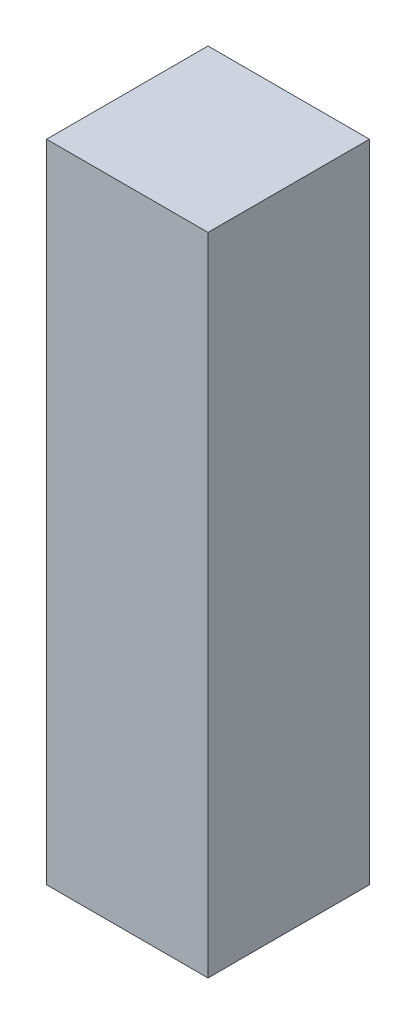
SolidWorks part; units mm, degrees
ref_plane "Front Plane" through (0, 0, 0) normal (0, 0, 1) x (1, 0, 0)
ref_plane "Top Plane" through (0, 0, 0) normal (0, 1, 0) x (1, 0, 0)
ref_plane "Right Plane" through (0, 0, 0) normal (1, 0, 0) x (0, 0, -1)
sketch "Sketch1" plane through (0, 0, 0) normal (0, 1, 0) x (1, 0, 0)
  line L1 (-6.35, -6.35) -> (6.35, -6.35)
  line L2 (-6.35, -6.35) -> (-6.35, 6.35)
  line L3 (-6.35, 6.35) -> (6.35, 6.35)
  line L4 (6.35, -6.35) -> (6.35, 6.35)
  line L5 (-6.35, -6.35) -> (6.35, 6.35) construction
  line L6 (-6.35, 6.35) -> (6.35, -6.35) construction
  point P0 (0, 0)
  dimension "D1" = 12.7
  dimension "D2" = 12.7
extrude "Boss-Extrude1" add sketch "Sketch1" along normal blind 50.8
sketch "Sketch4" plane through (0, 0, 0) normal (0, 0, 1) x (1, 0, 0)
  line L0 (0, 0) -> (0, 50.8) construction
  line L1 (6.35, 50.8) -> (-6.35, 50.8) construction
